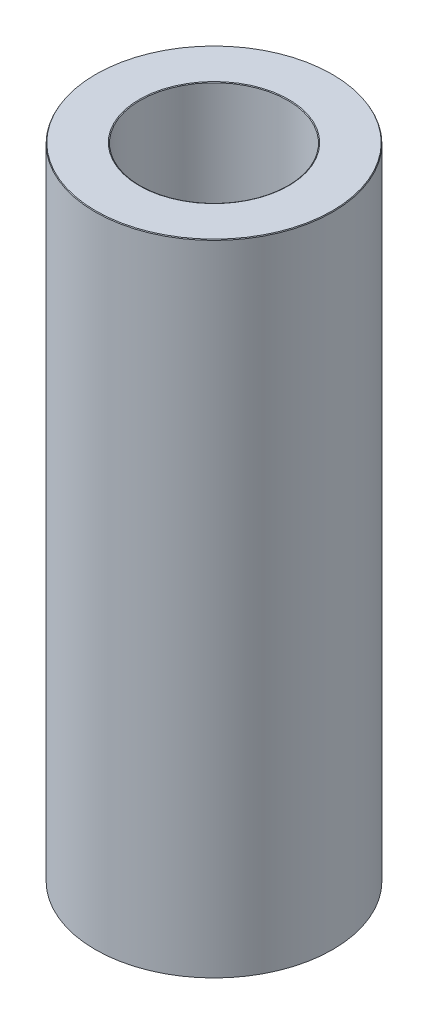
SolidWorks part; units mm, degrees
ref_plane "Front Plane" through (0, 0, 0) normal (0, 0, 1) x (1, 0, 0)
ref_plane "Top Plane" through (0, 0, 0) normal (0, 1, 0) x (1, 0, 0)
ref_plane "Right Plane" through (0, 0, 0) normal (1, 0, 0) x (0, 0, -1)
sketch "Sketch1" plane through (0, 0, 0) normal (0, 1, 0) x (1, 0, 0)
  circle A0 centre (0, 0) radius 40
  dimension "SLEEVE_OD" = 80
extrude "Boss-Extrude1" add sketch "Sketch1" along normal blind 215.6048
sketch "Sketch2" plane through (0, 0, 0) normal (0, 1, 0) x (1, 0, 0)
  circle A0 centre (0, 0) radius 24.9092
  dimension "BORE_D" = 49.8183
extrude "Cut-Extrude1" cut sketch "Sketch2" along normal through all
chamfer "Chamfer1" distance 0.2734 angle 30 4 edges at (0, 215.6048, 24.9092) (0, 0, 24.9092) (0, 0, 40) (0, 215.6048, 40) first distance on face at (0, 215.6048, 24.9092) first distance on face at (0, 0, 24.9092) first distance on face at (0, 215.6048, 40)
